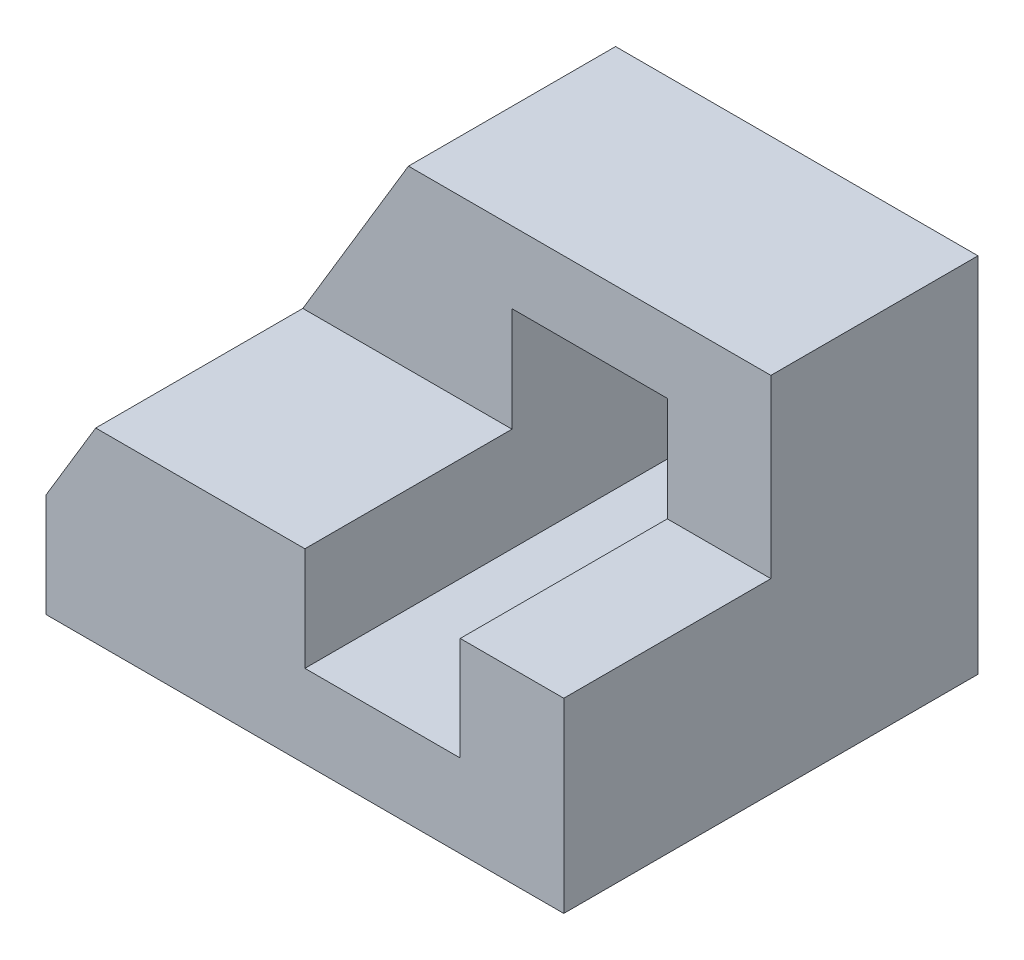
SolidWorks part; units mm, degrees
ref_plane "Front Plane" through (0, 0, 0) normal (0, 0, 1) x (1, 0, 0)
ref_plane "Top Plane" through (0, 0, 0) normal (0, 1, 0) x (1, 0, 0)
ref_plane "Right Plane" through (0, 0, 0) normal (1, 0, 0) x (0, 0, -1)
sketch "Sketch1" plane through (0, 0, 0) normal (0, 0, 1) x (1, 0, 0)
  line L0 (0, 0) -> (50, 0)
  line L1 (50, 0) -> (50, 35)
  line L2 (50, 35) -> (15, 35)
  line L3 (15, 35) -> (0, 10)
  line L4 (0, 10) -> (0, 0)
  line L5 (4.8, 18) -> (50, 18)
  line L7 (25, 28.0787) -> (40, 28.0787)
  line L8 (25, 28.0787) -> (25, 8)
  line L9 (25, 8) -> (40, 8)
  line L10 (40, 28.0787) -> (40, 8)
  line L11 (32.5, 18.0393) -> (32.5294, 18) construction
  line L12 (32.4706, 18) -> (32.5, 18.0393) construction
  point P8 (32.5, 18.0393)
  dimension "Width" = 50
  dimension "D4" = 35
  dimension "D3" = 35
  dimension "Left_H" = 10
  dimension "CutW" = 15
  dimension "Position_X" = 25
  dimension "D1" = 18
  dimension "D2" = 10
extrude "Boss-Extrude1" add sketch "Sketch1" along normal blind 40 contours L5 L10 L9 L8 L3 L4 L0 L1 region at (24.0754, 8.0126, 0)
extrude "Boss-Extrude2" add sketch "Sketch1<3>" along normal blind 20 contours L7 L10 L5 L1 L2 L3 L8 region at (45, 18.4829, 0)
sketch "Sketch1<3>" plane through (0, 0, 0) normal (0, 0, 1) x (1, 0, 0) same geometry as "Sketch1"
sketch "Sketch2" [suppressed] plane through (0, 35, 0) normal (0, 1, 0) x (1, 0, 0)
  circle A0 centre (35, -10) radius 5
  dimension "Diameter" = 10
extrude "Cut-Extrude1" [suppressed] cut sketch "Sketch2" against normal through all
equation "\"Width\"= 50"
equation "\"Position_x\"= 25"
equation "\"CutW\"=15"
equation "\"Left_H\"= 10"
equation "\"Diameter\"= 10"
equation "\"Depth\"= 40"
equation "\"D1\"= 20"
equation "\"D4\"=35"
equation "\"D2\"= 18"
equation "\"D3\"=10"
equation "\"Width@Sketch1\"=\"Width\""
equation "\"CutW@Sketch1\" = \"CutW\""
equation "\"Position_X@Sketch1\"=\"Position_x\""
equation "\"D4@Sketch1\" = \"D4\""
equation "\"Left_H@Sketch1\"=\"Left_H\""
equation "\"D1@Sketch1\"=\"D2\""
equation "\"D2@Sketch1\" = \"D3\""
equation "\"D3@Sketch1\"=\"D4\""
